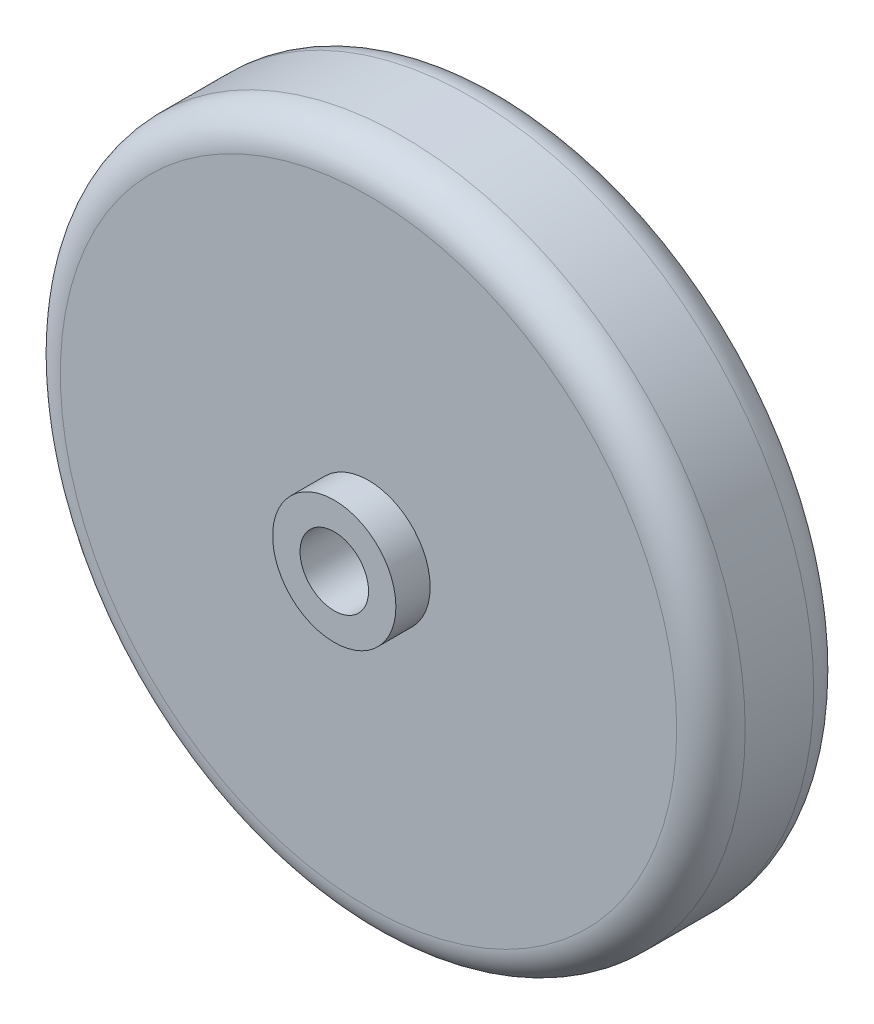
SolidWorks part; units mm, degrees
ref_plane "Front Plane" through (0, 0, 0) normal (0, 0, 1) x (1, 0, 0)
ref_plane "Top Plane" through (0, 0, 0) normal (0, 1, 0) x (1, 0, 0)
ref_plane "Right Plane" through (0, 0, 0) normal (1, 0, 0) x (0, 0, -1)
sketch "Sketch1" plane through (0, 0, 0) normal (0, 0, 1) x (1, 0, 0)
  circle A0 centre (0, 0) radius 50
  dimension "D1" = 100
extrude "Boss-Extrude1" add sketch "Sketch1" along normal blind 20
sketch "Sketch2" plane through (0, 0, 20) normal (0, 0, 1) x (1, 0, 0)
  circle A0 centre (0, 0) radius 9
  dimension "D1" = 18
extrude "Boss-Extrude2" add sketch "Sketch2" along normal blind 5 contours A0
sketch "Sketch3" plane through (0, 0, 0) normal (0, 0, -1) x (-1, 0, 0)
  line L0 (0, 0) -> (0, 40)
  line L1 (0, 0) -> (23.5114, 32.3607)
  line L2 (0, 0) -> (38.0423, 12.3607)
  line L3 (0, 0) -> (38.0423, -12.3607)
  line L4 (0, 0) -> (23.5114, -32.3607)
  line L5 (0, 0) -> (0, -40)
  line L6 (0, 0) -> (-23.5114, -32.3607)
  line L7 (0, 0) -> (-38.0423, -12.3607)
  line L8 (0, 0) -> (-38.0423, 12.3607)
  line L9 (0, 0) -> (-23.5114, 32.3607)
  line L10 (-5.8779, 8.0902) -> (-3.0966, 39.88)
  line L11 (5.8779, 8.0902) -> (3.0966, 39.88)
  line L12 (5.8779, 8.0902) -> (36.9712, 15.2686)
  line L13 (9.5106, -3.0902) -> (38.885, 9.3785)
  line L14 (9.5106, -3.0902) -> (25.9461, -30.4434)
  line L15 (0, -10) -> (20.9356, -34.0837)
  line L16 (0, -10) -> (-20.9356, -34.0837)
  line L17 (-9.5106, -3.0902) -> (-25.9461, -30.4434)
  line L18 (-9.5106, -3.0902) -> (-38.885, 9.3785)
  line L19 (-5.8779, 8.0902) -> (-36.9712, 15.2686)
  circle A0 centre (0, 0) radius 40
  circle A1 centre (0, 0) radius 10
  point P4 (-5.8779, 8.0902)
  point P6 (5.8779, 8.0902)
  point P16 (0, 0)
  point P17 (9.5106, -3.0902)
  point P18 (0, -10)
  point P19 (-9.5106, -3.0902)
  point P42 (0, 0)
  dimension "D1" = 80
  dimension "D2" = 20
  dimension "D4" = 10
  dimension "D3" = 10
  dimension "D5" = 5
extrude "Cut-Extrude4" cut sketch "Sketch3" against normal blind 10 contours L9 A0 L19 | L10 A0 L9 | L1 A0 L11 | L12 A0 L1 | L3 A0 L13 | L14 A0 L3 | L5 A0 L15 | L16 A0 L5 | L7 A0 L17 | L18 A0 L7 region at (-11.004, 27.4243, 0) region at (-22.6817, 18.94, 0) region at (-29.4825, -1.9908, 0) region at (-25.022, -15.7188, 0) region at (-7.2172, -28.6547, 0) region at (7.2172, -28.6547, 0) region at (25.022, -15.7188, 0) region at (29.4825, -1.9908, 0) region at (22.6817, 18.94, 0) region at (11.004, 27.4243, 0)
sketch "Sketch4" plane through (0, 0, 0) normal (0, 0, -1) x (-1, 0, 0)
  circle A0 centre (0, 0) radius 40
chamfer "Chamfer2" distance 2 angle 45 10 edges at (10.4678, -22.0419, 0) (-10.4678, -22.0419, 0) (-17.7283, -16.7668, 0) (-24.1978, 3.1442, 0) (-21.4245, 11.6794, 0) (-4.4872, 23.9851, 0) (17.7283, -16.7668, 0) (24.1978, 3.1442, 0) (4.4872, 23.9851, 0) (21.4245, 11.6794, 0)
fillet "Fillet1" radius 5 5 edges at (38.0423, -12.3607, 0) (0, -40, 0) (-38.0423, -12.3607, 0) (-23.5114, 32.3607, 0) (23.5114, 32.3607, 0)
fillet "Fillet2" radius 5 2 edges at (50, 0, 20) (50, 0, 0)
sketch "Sketch5" plane through (0, 0, 25) normal (0, 0, 1) x (1, 0, 0)
  circle A0 centre (0, 0) radius 5
  circle A1 centre (0, 0) radius 9 construction
  dimension "D1" = 10
extrude "Cut-Extrude5" cut sketch "Sketch5" against normal blind 15
